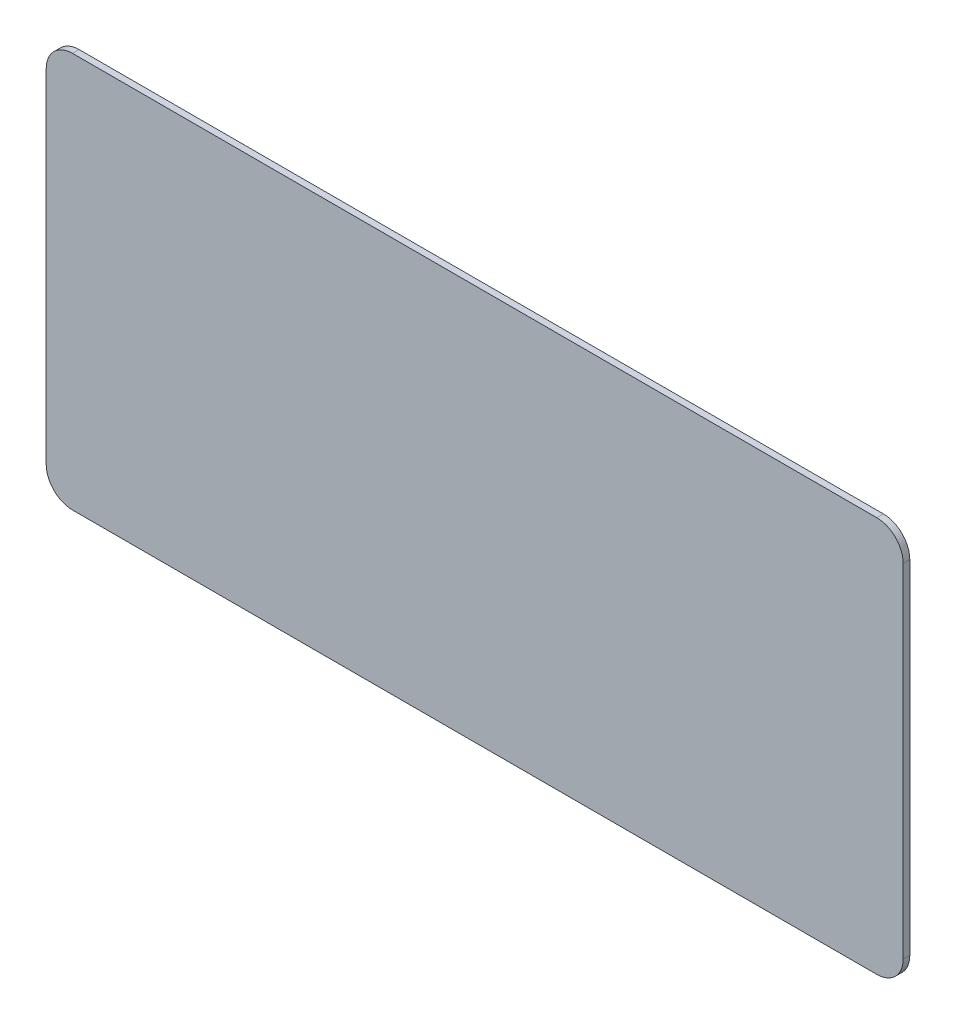
SolidWorks part; units mm, degrees
ref_plane "Front Plane" through (0, 0, 0) normal (0, 0, 1) x (1, 0, 0)
ref_plane "Top Plane" through (0, 0, 0) normal (0, 1, 0) x (1, 0, 0)
ref_plane "Right Plane" through (0, 0, 0) normal (1, 0, 0) x (0, 0, -1)
sketch "Sketch1" plane through (0, 0, 0) normal (0, 0, 1) x (1, 0, 0)
  line L0 (125.9407, 9.445) -> (125.9407, -9.555) construction
  line L1 (100.9407, 9.445) -> (150.9407, 9.445) construction
  line L2 (150.9407, -9.555) -> (100.9407, -9.555) construction
  line L3 (93.4407, 14.945) -> (93.4407, -15.055) construction
  line L4 (93.4407, -15.055) -> (158.4407, -15.055) construction
  line L5 (158.4407, -15.055) -> (158.4407, 14.945) construction
  line L6 (158.4407, 14.945) -> (93.4407, 14.945) construction
  line L7 (95.4407, 14.945) -> (95.4407, -15.055) construction
  line L8 (158.4407, -15.055) -> (93.4407, 14.945) construction
  line L9 (158.4407, 14.945) -> (93.4407, -15.055) construction
  line L10 (93.4407, -13.055) -> (158.4407, -13.055) construction
  line L11 (156.4407, -15.055) -> (156.4407, 14.945) construction
  line L12 (158.4407, 12.945) -> (93.4407, 12.945) construction
  line L13 (93.4407, -13.055) -> (93.4407, 12.945)
  line L14 (95.4407, 14.945) -> (156.4407, 14.945)
  line L15 (158.4407, 12.945) -> (158.4407, -13.055)
  line L16 (156.4407, -15.055) -> (95.4407, -15.055)
  arc A0 (93.4407, 12.945) -> (95.4407, 14.945) centre (95.4407, 12.945) cw
  arc A1 (156.4407, 14.945) -> (158.4407, 12.945) centre (156.4407, 12.945) cw
  arc A2 (158.4407, -13.055) -> (156.4407, -15.055) centre (156.4407, -13.055) cw
  arc A3 (95.4407, -15.055) -> (93.4407, -13.055) centre (95.4407, -13.055) cw
  point P6 (125.9407, -0.055)
  dimension "D1" = 65
  dimension "D2" = 30
  dimension "D3" = 2
extrude "Boss-Extrude1" add sketch "Sketch1" against normal blind 0.5
sketch "Sketch2" plane through (0, 0, -0.5) normal (0, 0, -1) x (-1, 0, 0)
  line L0 (-150.9407, 6.945) -> (-100.9407, 6.945) construction
  line L1 (-150.9407, -9.555) -> (-150.9407, 9.445) construction
  line L2 (-100.9407, -9.555) -> (-100.9407, 9.445) construction
  line L3 (-150.9407, -7.055) -> (-100.9407, -7.055) construction
  line L4 (-103.4407, 9.445) -> (-103.4407, -9.555) construction
  line L5 (-100.9407, 9.445) -> (-150.9407, 9.445) construction
  line L6 (-150.9407, -9.555) -> (-100.9407, -9.555) construction
  line L7 (-148.4407, 9.445) -> (-148.4407, -9.555) construction
  line L8 (-148.4407, 9.445) -> (-103.4407, 9.445)
  line L9 (-100.9407, 6.945) -> (-100.9407, -7.055)
  line L10 (-103.4407, -9.555) -> (-148.4407, -9.555)
  line L12 (-150.9407, -7.055) -> (-150.9407, 6.945)
  arc A0 (-150.9407, 6.945) -> (-148.4407, 9.445) centre (-148.4407, 6.945) cw
  arc A1 (-103.4407, 9.445) -> (-100.9407, 6.945) centre (-103.4407, 6.945) cw
  arc A2 (-103.4407, -9.555) -> (-100.9407, -7.055) centre (-103.4407, -7.055) ccw
  arc A3 (-148.4407, -9.555) -> (-150.9407, -7.055) centre (-148.4407, -7.055) cw
  dimension "D1" = 2.5
extrude "Boss-Extrude2" add sketch "Sketch2" along normal blind 0.5 separate body
